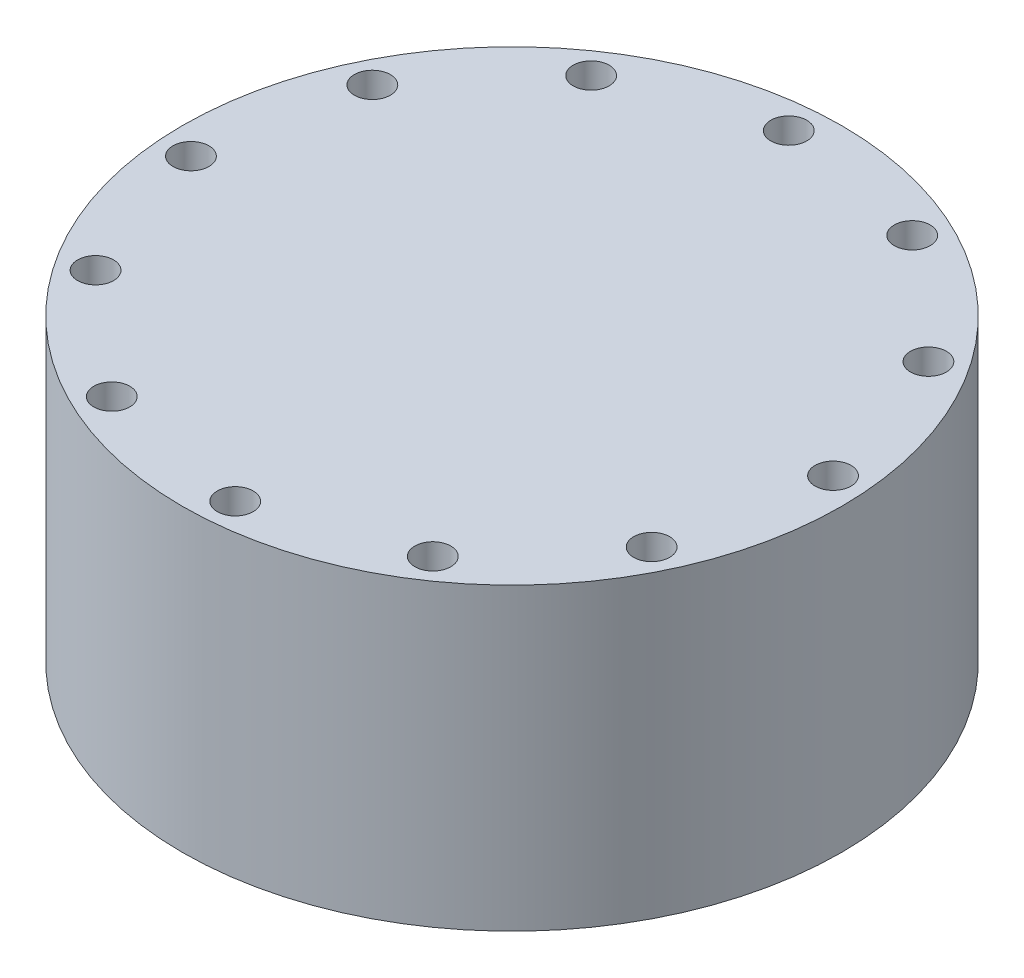
SolidWorks part; units mm, degrees
ref_plane "Front Plane" through (0, 0, 0) normal (0, 0, 1) x (1, 0, 0)
ref_plane "Top Plane" through (0, 0, 0) normal (0, 1, 0) x (1, 0, 0)
ref_plane "Right Plane" through (0, 0, 0) normal (1, 0, 0) x (0, 0, -1)
sketch "Sketch1" plane through (0, 0, 0) normal (0, 1, 0) x (1, 0, 0)
  circle A0 centre (0, 0) radius 27.5
  circle A1 centre (0, 0) radius 25 construction
  circle A2 centre (0, 0) radius 22.5
  circle A3 centre (-1.8468, 24.9317) radius 1.5
  circle A4 centre (10.8665, 22.5149) radius 1.5
  circle A5 centre (20.6681, 14.0652) radius 1.5
  circle A6 centre (24.9317, 1.8468) radius 1.5
  circle A7 centre (22.5149, -10.8665) radius 1.5
  circle A8 centre (14.0652, -20.6681) radius 1.5
  circle A9 centre (1.8468, -24.9317) radius 1.5
  circle A10 centre (-10.8665, -22.5149) radius 1.5
  circle A11 centre (-20.6681, -14.0652) radius 1.5
  circle A12 centre (-24.9317, -1.8468) radius 1.5
  circle A13 centre (-22.5149, 10.8665) radius 1.5
  circle A14 centre (-14.0652, 20.6681) radius 1.5
  point P31 (0, 0)
  dimension "D1" = 55
  dimension "D2" = 50
  dimension "D3" = 45
  dimension "D4" = 3
  dimension "D5" = 12
extrude "Boss-Extrude1" add sketch "Sketch1" along normal blind 25
sketch "Sketch2" plane through (0, 25, 0) normal (0, 1, 0) x (1, 0, 0)
  circle A0 centre (0, 0) radius 22.5
extrude "Boss-Extrude2" add sketch "Sketch2" against normal blind 3
